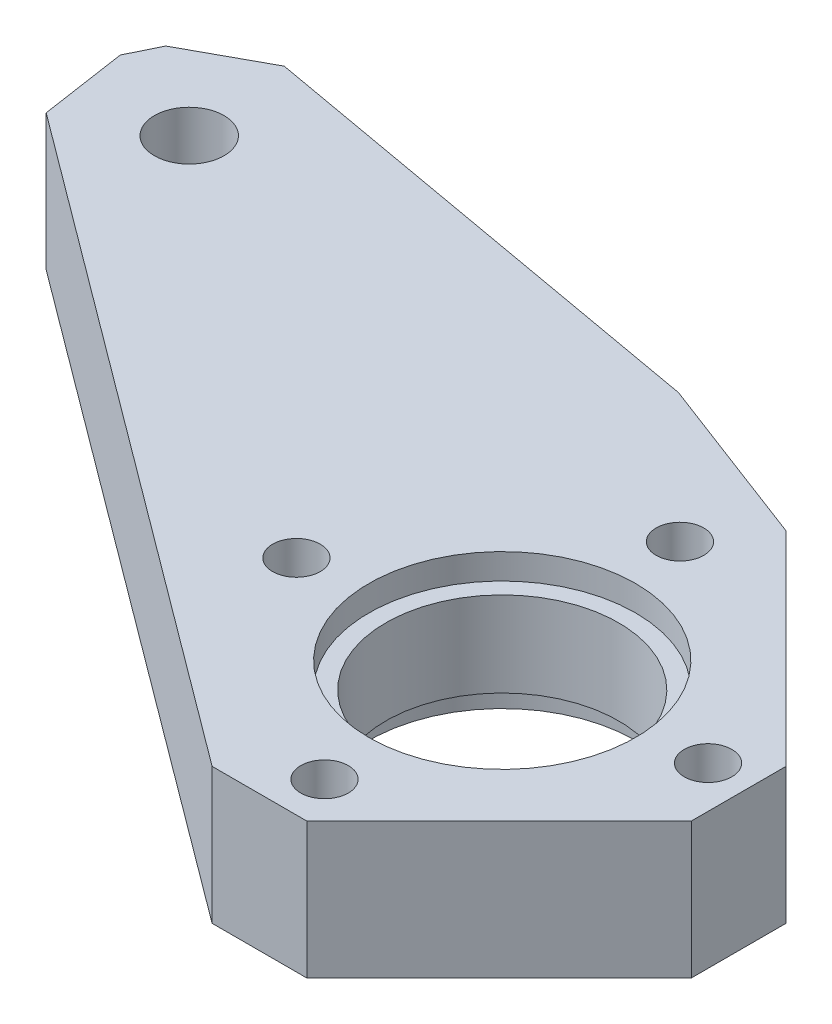
SolidWorks part; units mm, degrees
ref_plane "Front Plane" through (0, 0, 0) normal (0, 0, 1) x (1, 0, 0)
ref_plane "Top Plane" through (0, 0, 0) normal (0, 1, 0) x (1, 0, 0)
ref_plane "Right Plane" through (0, 0, 0) normal (1, 0, 0) x (0, 0, -1)
sketch "Sketch1" plane through (0, 0, 0) normal (0, 1, 0) x (1, 0, 0)
  line L0 (31.2261, 7.0808) -> (19.9124, -4.2329)
  line L1 (19.9124, -4.2329) -> (14.3424, -4.2329)
  line L2 (14.3424, -4.2329) -> (-23.8419, 24.1874)
  line L10 (31.2261, 7.0808) -> (31.2261, 12.6408)
  line L11 (31.2261, 12.6408) -> (19.2053, 24.6616)
  line L12 (19.2053, 24.6616) -> (9.0164, 28.5341)
  line L13 (-23.8419, 24.1874) -> (-24.6067, 29.3107)
  line L14 (-24.6067, 29.3107) -> (-23.7303, 31.1084)
  line L15 (9.0164, 28.5341) -> (-19.2183, 33.5685)
  line L18 (-23.7303, 31.1084) -> (-19.2183, 33.5685)
  dimension "D1" = 16
  dimension "D2" = 135
  dimension "D3" = 47.6
  dimension "D4" = 5.56
  dimension "D5" = 2
  dimension "D6" = 5.57
  dimension "D7" = 135
  dimension "D8" = 17
  dimension "D9" = 135
  dimension "D10" = 5.18
  dimension "D11" = 36.66
  dimension "D12" = 135.15
  dimension "D13" = 28.68
  dimension "D14" = 10.9
  dimension "D15" = 155.81
  dimension "D16" = 169.3
  dimension "D17" = 145.52
extrude "Boss-Extrude1" add sketch "Sketch1" along normal blind 8
sketch "Sketch2" plane through (0, 8, 0) normal (0, 1, 0) x (1, 0, 0)
  line L0 (-23.8419, 24.1874) -> (14.3424, -4.2329) construction
  line L1 (13.9114, 19.1552) -> (17.4834, 9.6972) construction
  line L2 (17.4834, 9.6972) -> (11.8363, 9.6972) construction
  line L3 (25.2157, 18.6512) -> (4.8853, -4.8913) construction
  line L4 (31.2261, 12.6408) -> (19.2053, 24.6616) construction
  line L5 (2.9673, 22.2328) -> (17.4834, 9.6972) construction
  circle A0 centre (17.4834, 9.6972) radius 6.85
  circle A1 centre (17.4834, 9.6972) radius 7.85
  circle A2 centre (-18.4687, 27.2314) radius 2.05
  circle A7 centre (16.6573, 20.9807) radius 1.4
  circle A8 centre (28.7669, 10.5233) radius 1.4
  circle A9 centre (6.1999, 8.8711) radius 1.4
  circle A10 centre (18.3095, -1.5863) radius 1.4
  point P19 (16.7882, 10.2147)
  point P23 (0, 0)
  dimension "D1" = 13.7
  dimension "D2" = 15.7
  dimension "D3" = 2.8
  dimension "D4" = 4.1
  dimension "D5" = 40
  dimension "D6" = 5.65
  dimension "D7" = 13.05
  dimension "D8" = 10.11
  dimension "D9" = 69.31
  dimension "D10" = 8
  dimension "D11" = 8
extrude "Cut-Extrude1" cut sketch "Sketch2" against normal blind 8 contours A2 | A0
extrude "Cut-Extrude2" cut sketch "Sketch2<4>" against normal blind 1.5 contours A1 A0 region at (9.8554, 8, -9.6972)
sketch "Sketch2<4>" plane through (0, 8, 0) normal (0, 1, 0) x (1, 0, 0) same geometry as "Sketch2"
extrude "Cut-Extrude3" cut sketch "Sketch2<5>" along normal blind 1.5 from offset 8 offset against normal yes
sketch "Sketch2<5>" plane through (0, 8, 0) normal (0, 1, 0) x (1, 0, 0) same geometry as "Sketch2"
extrude "Cut-Extrude4" cut sketch "Sketch2<6>" against normal blind 10 contours A7 | A8 | A10 | A9 region at (16.6573, 8, -20.9807) region at (28.7669, 8, -10.5233) region at (18.3095, 8, 1.5863)
sketch "Sketch2<6>" plane through (0, 8, 0) normal (0, 1, 0) x (1, 0, 0) same geometry as "Sketch2"
